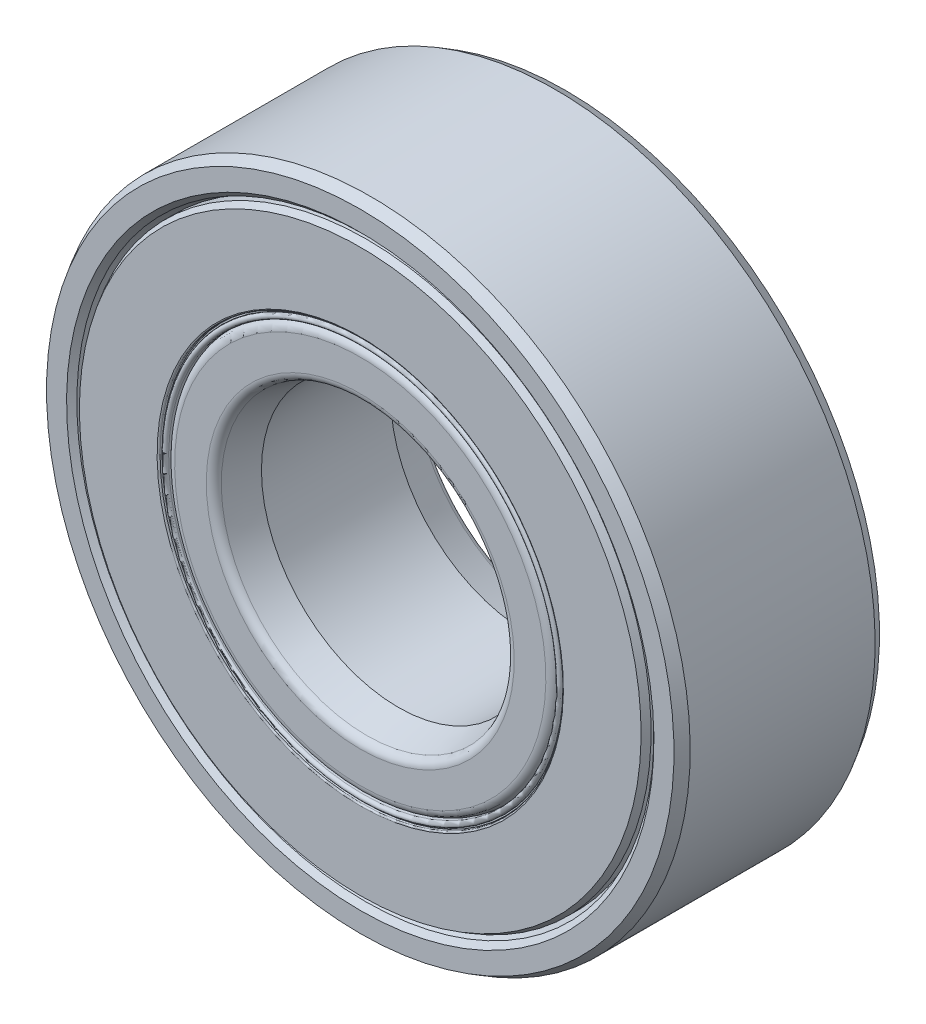
SolidWorks part; units mm, degrees
ref_plane "Front Plane" through (0, 0, 0) normal (0, 0, 1) x (1, 0, 0)
ref_plane "Top Plane" through (0, 0, 0) normal (0, 1, 0) x (1, 0, 0)
ref_plane "Right Plane" through (0, 0, 0) normal (1, 0, 0) x (0, 0, -1)
sketch "Sketch1" plane through (0, 0, 0) normal (0, 0, 1) x (1, 0, 0)
  line L0 (-11.1125, 0) -> (11.1125, 0) construction
  line L1 (-4.7625, 0) -> (4.7625, 0) construction
  circle A0 centre (0, 0) radius 4.7625 construction
  circle A1 centre (0, 0) radius 11.1125 construction
  point P3 (0, 0)
  point P6 (0, 0)
  point P7 (0, -4.7625)
  point P11 (0, -11.1125)
  point P12 (0, 4.7625)
  point P13 (0, 11.1125)
  dimension "OD" = 22.225
  dimension "ID" = 9.525
sketch "Sketch2" plane through (0, 0, 0) normal (1, 0, 0) x (0, 0, -1)
  line L0 (-3.5719, 11.1125) -> (3.5719, 11.1125) construction
  line L1 (0, 11.1125) -> (0, -11.1125) construction
  line L2 (3.2147, 11.1125) -> (-3.2147, 11.1125)
  line L3 (-3.2147, 11.1125) -> (-3.5719, 10.9063)
  line L4 (-3.5719, 10.9063) -> (-3.5719, 10.2098)
  line L5 (-3.0057, 9.8901) -> (-1.7936, 9.8901)
  line L6 (3.0057, 9.8901) -> (1.7936, 9.8901)
  line L7 (3.5719, 10.9063) -> (3.5719, 10.2098)
  line L8 (3.2147, 11.1125) -> (3.5719, 10.9063)
  line L9 (-1.7936, 9.8901) -> (-1.7936, 10.2976) construction
  line L10 (-1.7936, 10.2976) -> (-1.7936, 10.705) construction
  line L11 (0, 11.1125) -> (0, -11.1125) construction
  line L12 (-3.5719, 0) -> (3.5719, 0) construction
  line L13 (3.5719, 4.7625) -> (-3.5719, 4.7625) construction
  line L14 (-3.5719, 4.7625) -> (-3.5719, -4.7625) construction
  line L15 (-3.5719, -4.7625) -> (3.5719, -4.7625) construction
  line L16 (3.5719, 11.1125) -> (3.5719, -11.1125) construction
  line L17 (-1.7936, 10.705) -> (-1.7936, 11.1125) construction
  line L18 (-1.7936, 10.705) -> (0, 10.705) construction
  line L20 (-3.0057, 9.8901) -> (-3.3933, 10.0312)
  line L21 (-3.3933, 10.0312) -> (-3.5719, 10.2098)
  line L26 (3.3933, 10.0312) -> (3.5719, 10.2098)
  line L27 (3.0057, 9.8901) -> (3.3933, 10.0312)
  arc A0 (-1.7936, 9.8901) -> (1.7936, 9.8901) centre (0, 8.3238) cw
  circle A1 centre (0, 8.3238) radius 2.3813 construction
  point P17 (0, 0)
  point P21 (0, 11.1125)
  point P30 (0, -4.7625)
  dimension "Approx. Ball Dia." = 4.7625
  dimension "Width" = 7.1437
  dimension "For Shaft Diameter" = 9.525
  dimension "For Housing ID" = 22.225
  dimension "D4" = 19.7802
  dimension "D2" = 20
  dimension "D5" = 45
  dimension "D1" = 30
  dimension "D6" = 0.3572
  dimension "D7" = 0.1786
sketch "Sketch3" plane through (0, 0, 0) normal (1, 0, 0) x (0, 0, -1)
  line L14 (-3.0057, 9.8901) -> (-3.3933, 10.0312) construction
  line L15 (-3.3933, 10.0312) -> (-3.5719, 10.2098) construction
  line L16 (-3.5719, 10.9063) -> (-3.5719, 10.2098) construction
  line L17 (-3.2147, 11.1125) -> (-3.5719, 10.9063) construction
  line L18 (3.2147, 11.1125) -> (-3.2147, 11.1125) construction
  line L19 (3.2147, 11.1125) -> (3.5719, 10.9063) construction
  line L20 (3.5719, 10.9063) -> (3.5719, 10.2098) construction
  line L21 (3.3933, 10.0312) -> (3.5719, 10.2098) construction
  line L22 (3.0057, 9.8901) -> (3.3933, 10.0312) construction
  line L23 (3.0057, 9.8901) -> (1.7936, 9.8901) construction
  line L24 (-3.0057, 9.8901) -> (-1.7936, 9.8901) construction
  line L25 (-3.0057, 9.8901) -> (-3.3933, 10.0312)
  line L26 (-3.3933, 10.0312) -> (-3.5719, 10.2098)
  line L27 (-3.5719, 10.9063) -> (-3.5719, 10.2098)
  line L28 (-3.2147, 11.1125) -> (-3.5719, 10.9063)
  line L29 (3.2147, 11.1125) -> (-3.2147, 11.1125)
  line L30 (3.2147, 11.1125) -> (3.5719, 10.9063)
  line L31 (3.5719, 10.9063) -> (3.5719, 10.2098)
  line L32 (3.3933, 10.0312) -> (3.5719, 10.2098)
  line L33 (3.0057, 9.8901) -> (3.3933, 10.0312)
  line L34 (3.0057, 9.8901) -> (1.7936, 9.8901)
  line L35 (-3.0057, 9.8901) -> (-1.7936, 9.8901)
  arc A2 (1.7936, 9.8901) -> (-1.7936, 9.8901) centre (0, 8.3238) ccw construction
  arc A3 (1.7936, 9.8901) -> (-1.7936, 9.8901) centre (0, 8.3238) ccw
revolve "Revolve1" add sketch "Sketch3" angle 360 about L12
sketch "Sketch4" plane through (0, 0, 0) normal (1, 0, 0) x (0, 0, -1)
  line L0 (0, 11.1125) -> (0, -11.1125) construction
  line L1 (0, 11.1125) -> (0, -11.1125) construction
  line L2 (-2.2445, 4.7625) -> (-3.3455, 5.0575)
  line L3 (-3.5719, 5.3525) -> (-3.5719, 6.452)
  line L4 (3.5719, -10.9063) -> (3.5719, 10.9063) construction
  line L5 (-3.2665, 6.7575) -> (-1.7936, 6.7575)
  line L6 (-2.2445, 4.7625) -> (2.2445, 4.7625)
  line L7 (3.5719, 10.9063) -> (3.5719, 10.2098) construction
  line L8 (2.2445, 4.7625) -> (3.3455, 5.0575)
  line L9 (0, 10.705) -> (0, 4.7625) construction
  line L10 (3.5719, 5.3525) -> (3.5719, 6.452)
  line L11 (3.2665, 6.7575) -> (1.7936, 6.7575)
  line L12 (2.2445, 4.7625) -> (2.2445, 5.0575) construction
  line L13 (2.2445, 5.0575) -> (2.2445, 5.3525) construction
  line L14 (2.2445, 5.3525) -> (2.2445, 5.6475) construction
  line L15 (2.2445, 5.6475) -> (2.2445, 5.9425) construction
  circle A0 centre (0, 8.3238) radius 2.3812 construction
  arc A1 (1.7936, 6.7575) -> (-1.7936, 6.7575) centre (0, 8.3238) cw
  arc A2 (3.5719, 6.452) -> (3.2665, 6.7575) centre (3.2665, 6.452) ccw
  arc A3 (-3.5719, 6.452) -> (-3.2665, 6.7575) centre (-3.2665, 6.452) cw
  arc A4 (3.3455, 5.0575) -> (3.5719, 5.3525) centre (3.2665, 5.3525) ccw
  arc A5 (-3.3455, 5.0575) -> (-3.5719, 5.3525) centre (-3.2665, 5.3525) cw
  point P14 (3.5719, 5.1182)
  point P36 (0, 5.9425)
  dimension "D1" = 15
revolve "Revolve2" add sketch "Sketch4" angle 360 about L12
sketch "Sketch5" plane through (0, 0, 0) normal (1, 0, 0) x (0, 0, -1)
  line L0 (-2.3812, 8.3238) -> (2.3812, 8.3238)
  arc A2 (-2.3812, 8.3238) -> (2.3812, 8.3238) centre (0, 8.3238) cw
  arc A3 (1.7936, 9.8901) -> (-1.7936, 9.8901) centre (0, 8.3238) ccw construction
revolve "Revolve3" add sketch "Sketch5" angle 360 about L0
pattern_circular "CirPattern1" count 8 over 360 about axis through (0, 0, 3.5719) along (0, 0, -1) of bodies 104
sketch "Sketch6" plane through (0, 0, 0) normal (1, 0, 0) x (0, 0, -1)
  line L1 (-3.3519, 9.8901) -> (-2.3812, 9.8901)
  line L2 (-3.5719, 9.7631) -> (-3.5719, 7.0623)
  line L3 (-3.5211, 7.0115) -> (-2.3812, 7.0115)
  line L4 (-2.3812, 9.8901) -> (-2.3812, 7.0115)
  line L5 (-3.5719, 5.3525) -> (-3.5719, 6.452) construction
  line L6 (-3.2147, 11.1125) -> (-3.5719, 10.9063) construction
  line L7 (0, 11.1125) -> (0, 4.7625) construction
  line L8 (3.5211, 7.0115) -> (2.3813, 7.0115)
  line L9 (2.3813, 9.8901) -> (2.3813, 7.0115)
  line L10 (3.3519, 9.8901) -> (2.3813, 9.8901)
  line L11 (3.5719, 9.7631) -> (3.5719, 7.0623)
  line L13 (-3.2665, 6.7575) -> (-1.7936, 6.7575) construction
  line L14 (-3.5719, 9.7631) -> (-3.3519, 9.8901)
  line L15 (-3.0057, 9.8901) -> (-1.7936, 9.8901) construction
  line L16 (3.5719, 9.7631) -> (3.3519, 9.8901)
  arc A0 (-3.5719, 7.0623) -> (-3.5211, 7.0115) centre (-3.5211, 7.0623) ccw
  circle A1 centre (0, 8.3238) radius 2.3812 construction
  arc A2 (3.5719, 7.0623) -> (3.5211, 7.0115) centre (3.5211, 7.0623) cw
  point P26 (-3.5719, 7.0115)
  dimension "D3" = 0.0508
  dimension "D1" = 0.254
  dimension "D2" = 0.127
revolve "Revolve4" add sketch "Sketch6" angle 360 about L12
sketch "Sketch7" plane through (0, 0, 0) normal (1, 0, 0) x (0, 0, -1)
  line L3 (-2.3812, 7.0115) -> (-3.3937, 7.0115)
  line L4 (-3.5211, 7.0115) -> (-2.3812, 7.0115) construction
  line L7 (0, 5.9425) -> (0, 4.7625) construction
  line L8 (0, 11.1125) -> (0, -11.1125) construction
  line L21 (-3.3937, 7.0115) -> (-3.4562, 7.0004)
  line L22 (-3.4516, 6.948) -> (-3.4766, 6.948)
  line L23 (-3.4766, 6.7575) -> (-2.3812, 6.7575)
  line L24 (-2.3812, 6.7575) -> (-2.3812, 7.0115)
  line L25 (-3.2665, 6.7575) -> (-1.7936, 6.7575) construction
  line L26 (-3.5719, 7.0623) -> (-3.5719, 6.7575) construction
  line L27 (-3.5719, 6.7575) -> (-3.4766, 6.7575) construction
  line L28 (-3.3937, 7.0115) -> (-3.3937, 6.948) construction
  line L29 (-3.3937, 6.948) -> (-3.3937, 6.8845) construction
  line L30 (-3.3937, 6.8845) -> (-3.3937, 6.821) construction
  line L31 (-3.3937, 6.821) -> (-3.3937, 6.7575) construction
  circle A2 centre (0, 8.3238) radius 2.3812 construction
  arc A9 (-3.4562, 7.0004) -> (-3.4516, 6.948) centre (-3.4516, 6.9744) ccw
  arc A10 (-3.4766, 6.948) -> (-3.4766, 6.7575) centre (-3.4766, 6.8527) ccw
  dimension "D1" = 0.025
  dimension "D2" = 10
revolve "Revolve5" add sketch "Sketch7" angle 360 about L12
equation "\"D4@Sketch2\"=\"OD@Sketch1\"*.89"
equation "\"D1@Sketch6\"=(\"OD@Sketch1\"-\"ID@Sketch1\")*.02"
equation "\"D2@Sketch6\"=\"D1@Sketch6\"*.5"
equation "\"D3@Sketch6\"=\"D1@Sketch6\"*.2"
equation "\"D6@Sketch2\"=\"Width@Sketch2\"*.05"
equation "\"D7@Sketch2\"=\"D6@Sketch2\"*.5"
equation "\"D1@CirPattern1\" =  ( pi * \"OD@Sketch1\" )  * .5625 / \"Approx. Ball Dia.@Sketch2\""
equation "\"Approx. Ball Dia.@Sketch2\"=(\"OD@Sketch1\"-\"ID@Sketch1\")*.5*.75"
